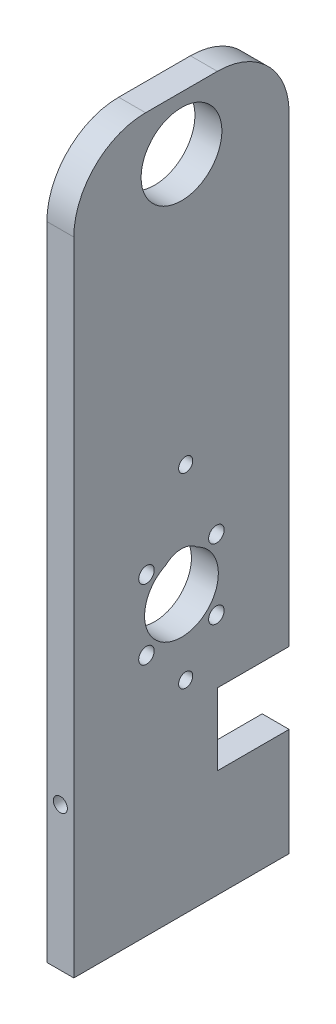
SolidWorks part; units mm, degrees
ref_plane "Front Plane" through (0, 0, 0) normal (0, 0, 1) x (1, 0, 0)
ref_plane "Top Plane" through (0, 0, 0) normal (0, 1, 0) x (1, 0, 0)
ref_plane "Right Plane" through (0, 0, 0) normal (1, 0, 0) x (0, 0, -1)
sketch "Sketch1" plane through (0, 0, 0) normal (0, 1, 0) x (1, 0, 0)
  line L1 (-4.7625, 38.1) -> (4.7625, 38.1)
  line L2 (-4.7625, 38.1) -> (-4.7625, -38.1)
  line L3 (-4.7625, -38.1) -> (4.7625, -38.1)
  line L4 (4.7625, 38.1) -> (4.7625, -38.1)
  line L5 (-4.7625, 38.1) -> (4.7625, -38.1) construction
  line L6 (-4.7625, -38.1) -> (4.7625, 38.1) construction
  point P0 (0, 0)
  dimension "D1" = 76.2
  dimension "D2" = 9.525
extrude "Boss-Extrude1" add sketch "Sketch1" along normal mid plane 252.476
sketch "Sketch3" plane through (-4.7625, 0, 0) normal (-1, 0, 0) x (0, 0, 1)
  line L0 (-45.1772, -15.4437) -> (44.4211, -15.4437) construction
  line L1 (-45.1772, -40.1878) -> (44.4211, -40.1878) construction
  line L2 (-38.1, 126.238) -> (38.1, 126.238) construction
  line L3 (-45.1772, -27.813) -> (44.4211, -27.813) construction
  line L4 (-12.3658, -8.7664) -> (-12.3658, -58.1325) construction
  line L5 (12.3748, -8.7664) -> (12.3748, -58.1325) construction
  line L6 (0, -8.7664) -> (0, -58.1325) construction
  circle A0 centre (0, 107.188) radius 14.2875
  circle A1 centre (-12.3658, -15.4437) radius 2.75
  circle A2 centre (12.3748, -15.4437) radius 2.75
  circle A3 centre (-12.3658, -40.1878) radius 2.75
  circle A4 centre (12.3748, -40.1878) radius 2.75
  circle A5 centre (0, -27.813) radius 13.0556
  point P12 (-38.1, 126.238)
  dimension "D1" = 28.575
  dimension "D2" = 19.05
  dimension "D3" = 12.3658
  dimension "D4" = 12.3748
  dimension "D7" = 26.1112
  dimension "D8" = 5.5
  dimension "D5" = 12.3693
  dimension "D6" = 12.3748
  dimension "D9" = 24.7406
extrude "Cut-Extrude2" cut sketch "Sketch3" against normal blind 45.974
fillet "Fillet1" radius 25.4 2 edges at (0, 126.238, 38.1) (0, 126.238, -38.1)
sketch "Sketch4" plane through (-4.7625, 0, 0) normal (-1, 0, 0) x (0, 0, 1)
  line L0 (-38.1, 100.838) -> (-38.1, -126.238) construction
  circle A0 centre (-1.5, 11.3124) radius 2.5
  circle A1 centre (-1.5, -54.6876) radius 2.5
  circle A2 centre (0, -21.6876) radius 7.9248
  dimension "D4" = 36.6
  dimension "D5" = 5
  dimension "D2" = 15.8496
  dimension "D1" = 66
  dimension "D3" = 33
  dimension "D6" = 1.5
  dimension "D7" = 1.5
  dimension "D8" = 38.1
extrude "Cut-Extrude3" cut sketch "Sketch4" against normal through all
sketch "Sketch5" plane through (-4.7625, 0, 0) normal (-1, 0, 0) x (0, 0, 1)
  line L1 (-38.1, 100.838) -> (-38.1, -126.238) construction
  line L2 (-38.1, -62.738) -> (-12.7, -62.738)
  line L3 (-38.1, -62.738) -> (-38.1, -88.138)
  line L4 (-38.1, -88.138) -> (-12.7, -88.138)
  line L6 (-12.7, -62.738) -> (-12.7, -88.138)
extrude "Cut-Extrude4" cut sketch "Sketch5" against normal through all contours L2 L6 L4 L3
hole_wizard "Tap Drill for M6x1.0 Tap1" positions "Sketch7" profile "Sketch6" hole size "M6x1.0" standard "ANSI Metric" end condition through all
sketch "Sketch7" plane through (0, 0, -12.7) normal (0, 0, -1) x (-1, 0, 0)
  line L0 (-4.7625, -62.738) -> (4.7625, -62.738) construction
  point P0 (0, -75.438)
  dimension "D1" = 12.7
sketch "Sketch6" plane through (0, -75.438, -12.7) normal (1, 0, 0) x (0, 1, 0)
  line L0 (0, 0) -> (0, 50.8)
  line L1 (0, 50.8) -> (2.5, 50.8)
  line L2 (2.5, 50.8) -> (2.5, 0)
  line L5 (2.5, 0) -> (0, 0)
  line L11 (0, -6.35) -> (0, 107.95) construction
  dimension "Thru Hole Dia." = 5
  dimension "Thru Hole Depth" = 50.8
